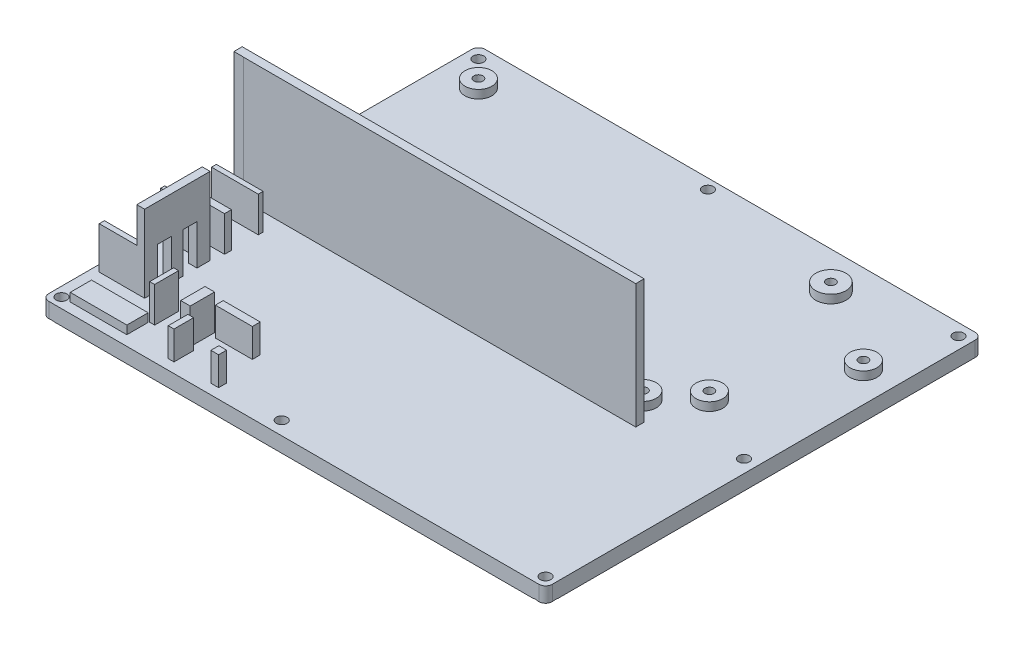
SolidWorks part; units mm, degrees
ref_plane "Front Plane" through (0, 0, 0) normal (0, 0, 1) x (1, 0, 0)
ref_plane "Top Plane" through (0, 0, 0) normal (0, 1, 0) x (1, 0, 0)
ref_plane "Right Plane" through (0, 0, 0) normal (1, 0, 0) x (0, 0, -1)
sketch "Sketch1" plane through (0, 0, 0) normal (0, 1, 0) x (1, 0, 0)
  line L1 (-64.1325, 54.3443) -> (85.8675, 54.3443)
  line L2 (-64.1325, 54.3443) -> (-64.1325, -75.6557)
  line L3 (-64.1325, -75.6557) -> (85.8675, -75.6557)
  line L4 (85.8675, 54.3443) -> (85.8675, -75.6557)
  dimension "D1" = 130
  dimension "D2" = 150
extrude "Boss-Extrude1" add sketch "Sketch1" along normal blind 2.5
sketch "Sketch2" plane through (0, 0, 0) normal (0, -1, 0) x (1, 0, 0)
  line L4 (-64.1325, 75.6557) -> (-64.1325, -54.3443)
  line L5 (-64.1325, -54.3443) -> (85.8675, -54.3443)
  line L6 (85.8675, -54.3443) -> (85.8675, 75.6557)
  line L7 (85.8675, 75.6557) -> (-64.1325, 75.6557)
  line L8 (-64.1325, 75.6557) -> (-64.1325, -54.3443)
  line L9 (-64.1325, -54.3443) -> (85.8675, -54.3443)
  line L10 (85.8675, -54.3443) -> (85.8675, 75.6557)
  line L11 (85.8675, 75.6557) -> (-64.1325, 75.6557)
  dimension "D1" = 0
extrude "Boss-Extrude2" add sketch "Sketch2" along normal blind 2
sketch "Sketch3" plane through (0, 2.5, 0) normal (0, 1, 0) x (1, 0, 0)
  line L1 (-51.1325, -42.2803) -> (-48.6325, -42.2803)
  line L2 (-51.1325, -42.2803) -> (-51.1325, -59.0608)
  line L3 (-51.1325, -59.0608) -> (-48.6325, -59.0608)
  line L4 (-48.6325, -42.2803) -> (-48.6325, -59.0608)
  dimension "D1" = 2.5
extrude "Boss-Extrude3" add sketch "Sketch3" along normal up to surface (12 mm away) up to face at (10.8675, 0.25, -54.3443)
sketch "Sketch4" plane through (0, 14.5, 0) normal (0, 1, 0) x (1, 0, 0)
  line L1 (-52.8026, -45.0022) -> (-45.803, -45.0022)
  line L2 (-52.8026, -45.0022) -> (-52.8026, -49.217)
  line L3 (-52.8026, -49.217) -> (-45.803, -49.217)
  line L4 (-45.803, -45.0022) -> (-45.803, -49.217)
  line L5 (-52.351, -52.6039) -> (-45.803, -52.6039)
  line L6 (-52.351, -52.6039) -> (-52.351, -56.7811)
  line L7 (-52.351, -56.7811) -> (-45.803, -56.7811)
  line L8 (-45.803, -52.6039) -> (-45.803, -56.7811)
extrude "Cut-Extrude1" cut sketch "Sketch4" against normal up to surface (12 mm away) up to face at (10.8675, 2.5, 10.6557)
sketch "Sketch5" plane through (0, 2.5, 0) normal (0, 1, 0) x (1, 0, 0)
  line L1 (-48.6325, -59.0608) -> (-62.1535, -59.0608)
  line L2 (-48.6325, -59.0608) -> (-48.6325, -60.6035)
  line L3 (-48.6325, -60.6035) -> (-62.1535, -60.6035)
  line L4 (-62.1535, -59.0608) -> (-62.1535, -60.6035)
  line L5 (-48.6325, -42.2803) -> (-62.1535, -42.2803)
  line L6 (-48.6325, -42.2803) -> (-48.6325, -41.0981)
  line L7 (-48.6325, -41.0981) -> (-62.1535, -41.0981)
  line L8 (-62.1535, -42.2803) -> (-62.1535, -41.0981)
extrude "Boss-Extrude4" add sketch "Sketch5" along normal blind 12.5
sketch "Sketch6" plane through (0, 2.5, 0) normal (0, 1, 0) x (1, 0, 0)
  line L1 (-58.7479, -66.3049) -> (-41.8814, -66.3049)
  line L2 (-58.7479, -66.3049) -> (-58.7479, -73.4288)
  line L3 (-58.7479, -73.4288) -> (-41.8814, -73.4288)
  line L4 (-41.8814, -66.3049) -> (-41.8814, -73.4288)
extrude "Boss-Extrude5" add sketch "Sketch6" along normal blind 2.5
sketch "Sketch7" plane through (0, 2.5, 0) normal (0, 1, 0) x (1, 0, 0)
  line L1 (-48.0669, -27.3064) -> (-62.0002, -27.3064)
  line L2 (-48.0669, -27.3064) -> (-48.0669, -25.8469)
  line L3 (-48.0669, -25.8469) -> (-62.0002, -25.8469)
  line L4 (-62.0002, -27.3064) -> (-62.0002, -25.8469)
  line L5 (-62.0002, -35.2912) -> (-48.0669, -35.2912)
  line L6 (-62.0002, -35.2912) -> (-62.0002, -37.3606)
  line L7 (-62.0002, -37.3606) -> (-48.0669, -37.3606)
  line L8 (-48.0669, -35.2912) -> (-48.0669, -37.3606)
extrude "Boss-Extrude6" add sketch "Sketch7" along normal blind 10.5
sketch "Sketch8" plane through (0, 2.5, 0) normal (0, 1, 0) x (1, 0, 0)
  line L0 (-32.1814, -59.0557) -> (-32.1814, -66.4557) construction
  line L1 (-40.2133, -58.9107) -> (-41.6789, -58.9107)
  line L2 (-40.2133, -58.9107) -> (-40.2133, -66.0309)
  line L3 (-40.2133, -66.0309) -> (-41.6789, -66.0309)
  line L4 (-41.6789, -58.9107) -> (-41.6789, -66.0309)
  line L5 (-32.1814, -59.0557) -> (-29.3436, -59.0557)
  line L6 (-32.1814, -59.0557) -> (-32.1814, -66.3049)
  line L7 (-32.1814, -66.3049) -> (-29.3436, -66.3049)
  line L8 (-29.3436, -59.0557) -> (-29.3436, -66.3049)
extrude "Boss-Extrude8" add sketch "Sketch8" along normal blind 10.5
sketch "Sketch9" plane through (0, 2.5, 0) normal (0, 1, 0) x (1, 0, 0)
  line L0 (-16.8443, -60.6557) -> (-16.8443, -75.6557) construction
  line L1 (-27.8395, -60.3242) -> (-16.8133, -60.3242)
  line L2 (-27.8395, -60.3242) -> (-27.8395, -57.991)
  line L3 (-27.8395, -57.991) -> (-16.8133, -57.991)
  line L4 (-16.8133, -60.3242) -> (-16.8133, -57.991)
  line L5 (-16.8443, -70.2591) -> (-14.5538, -70.2591)
  line L6 (-16.8443, -70.2591) -> (-16.8443, -73.3006)
  line L7 (-16.8443, -73.3006) -> (-14.5538, -73.3006)
  line L8 (-14.5538, -70.2591) -> (-14.5538, -73.3006)
  line L11 (-29.5556, -66.7933) -> (-27.8395, -66.7933)
  line L12 (-29.5556, -66.7933) -> (-29.5556, -73.75)
  line L13 (-29.5556, -73.75) -> (-27.8395, -73.75)
  line L14 (-27.8395, -66.7933) -> (-27.8395, -73.75)
extrude "Boss-Extrude9" add sketch "Sketch9" along normal blind 8.5
sketch "Sketch10" plane through (0, 2.5, 0) normal (0, 1, 0) x (1, 0, 0)
  line L1 (-60.7382, -72.6486) -> (3.4124, -72.6486)
  line L2 (-60.7382, -72.6486) -> (-60.7382, -74.3978)
  line L3 (-60.7382, -74.3978) -> (3.4124, -74.3978)
  line L4 (3.4124, -72.6486) -> (3.4124, -74.3978)
extrude "Cut-Extrude2" cut sketch "Sketch10" along normal blind 22
sketch "Sketch11" plane through (0, 2.5, 0) normal (0, 1, 0) x (1, 0, 0)
  circle A0 centre (61.8675, -2.8557) radius 4
  circle A1 centre (61.8675, -2.8557) radius 1.75 construction
  circle A2 centre (76.8675, 28.0443) radius 4
  circle A3 centre (76.8675, 28.0443) radius 1.75 construction
  circle A4 centre (51.8675, 43.3443) radius 4.5
  circle A5 centre (51.8675, -12.6557) radius 4
  circle A6 centre (-53.1325, -12.6557) radius 4
  circle A7 centre (-53.1325, 43.3443) radius 4
  dimension "D1" = 8
  dimension "D2" = 8
  dimension "D3" = 8
  dimension "D4" = 8
  dimension "D5" = 9
  dimension "D6" = 8
extrude "Boss-Extrude10" add sketch "Sketch11" along normal blind 2.5
sketch "Sketch12" plane through (0, 5, 0) normal (0, 1, 0) x (1, 0, 0)
  circle A0 centre (-53.2085, -12.7313) radius 1.35
  circle A1 centre (-53.1325, 43.3443) radius 1.35
  circle A2 centre (51.8675, 43.3443) radius 1.35
  circle A3 centre (51.8675, -12.6557) radius 1.35
  circle A4 centre (61.8675, -2.8557) radius 1.35
  circle A5 centre (76.8675, 28.0443) radius 1.35
  dimension "D1" = 2.7
  dimension "D2" = 2.7
  dimension "D3" = 2.7
  dimension "D4" = 2.7
  dimension "D5" = 2.7
  dimension "D6" = 2.7
extrude "Cut-Extrude3" cut sketch "Sketch12" against normal blind 5
sketch "Sketch13" plane through (0, -2, 0) normal (0, -1, 0) x (1, 0, 0)
  circle A0 centre (-61.3325, 72.6557) radius 1.6
  circle A1 centre (3.2544, 71.6557) radius 1.6
  circle A2 centre (82.8675, 72.6557) radius 1.6
  circle A3 centre (82.3675, -50.8443) radius 1.6
  circle A4 centre (-60.6325, -50.8443) radius 1.6
  circle A5 centre (7.2229, -51.3443) radius 1.6
  circle A6 centre (-60.1325, 21.1755) radius 1.6
  circle A7 centre (82.055, 12.7393) radius 1.6
  dimension "D1" = 3.2
  dimension "D2" = 3.2
  dimension "D3" = 3.2
  dimension "D4" = 3.2
  dimension "D5" = 3.2
  dimension "D6" = 3.2
  dimension "D7" = 3.2
  dimension "D8" = 3.2
extrude "Cut-Extrude4" cut sketch "Sketch13" against normal blind 9
chamfer "Chamfer1" distance 1.5 angle 45 8 edges at (3.2544, -2, 70.0557) (-61.3325, -2, 71.0557) (82.8675, -2, 71.0557) (82.055, -2, 11.1393) (82.3675, -2, -52.4443) (7.2229, -2, -52.9443) (-60.6325, -2, -52.4443) (-60.1325, -2, 19.5755)
fillet "Fillet1" radius 2 4 edges at (85.8675, 0.25, -54.3443) (-64.1325, 0.25, -54.3443) (-64.1325, 0.25, 75.6557) (85.8675, 0.25, 75.6557)
sketch "Sketch14" plane through (0, 14.5, 0) normal (0, 1, 0) x (1, 0, 0)
  line L0 (-62.1535, -60.6035) -> (-48.6325, -60.6035) construction
  line L1 (-48.6325, -41.0981) -> (-50.9587, -41.0981)
  line L2 (-48.6325, -41.0981) -> (-48.6325, -60.6035)
  line L3 (-48.6325, -60.6035) -> (-50.9587, -60.6035)
  line L4 (-50.9587, -41.0981) -> (-50.9587, -60.6035)
extrude "Boss-Extrude11" add sketch "Sketch14" along normal blind 11
sketch "Sketch15" plane through (0, 2.5, 0) normal (0, 1, 0) x (1, 0, 0)
  line L1 (-59.0942, -18.1627) -> (57.7408, -18.1627)
  line L2 (-59.0942, -18.1627) -> (-59.0942, -20.6627)
  line L3 (-59.0942, -20.6627) -> (57.7408, -20.6627)
  line L4 (57.7408, -18.1627) -> (57.7408, -20.6627)
  dimension "D1" = 2.5
extrude "Boss-Extrude12" add sketch "Sketch15" along normal blind 37
sketch "Sketch16" plane through (0, 39.5, 0) normal (0, 1, 0) x (1, 0, 0)
  line L1 (-59.0942, -18.1627) -> (-62.0095, -18.1627)
  line L2 (-59.0942, -18.1627) -> (-59.0942, -20.6227)
  line L3 (-59.0942, -20.6227) -> (-62.0095, -20.6227)
  line L4 (-62.0095, -18.1627) -> (-62.0095, -20.6227)
extrude "Boss-Extrude13" add sketch "Sketch16" against normal blind 33
